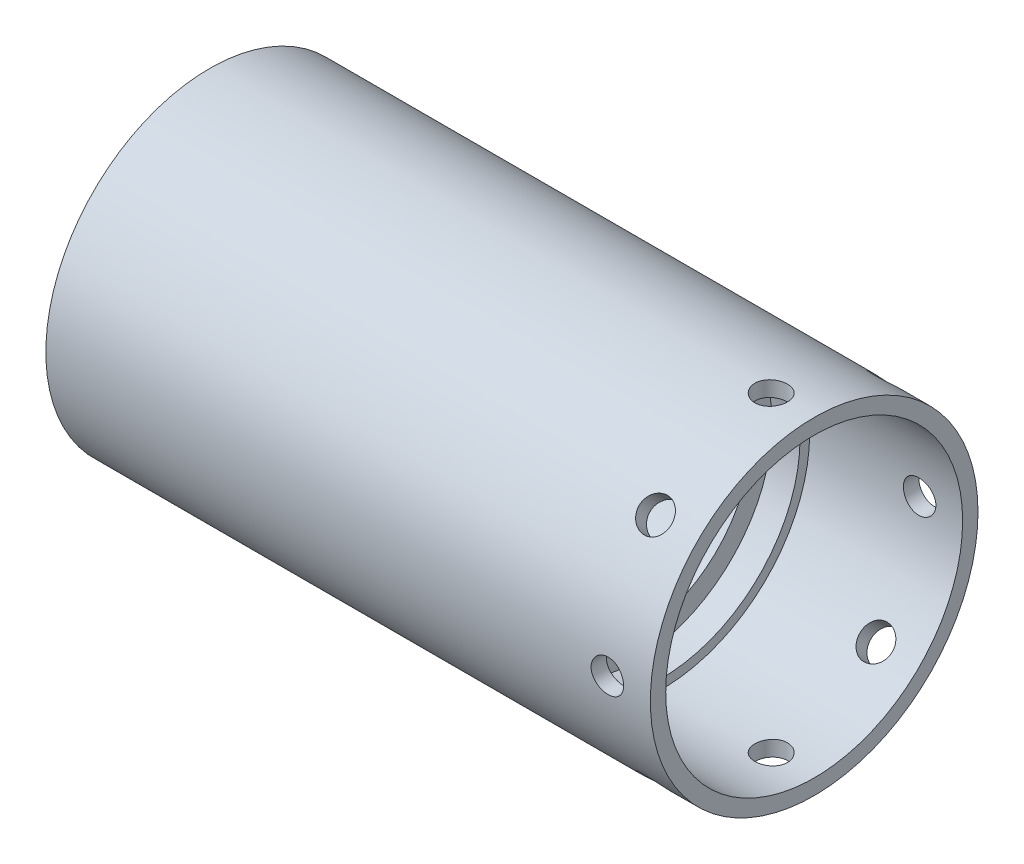
SolidWorks part; units mm, degrees
ref_plane "Front Plane" through (0, 0, 0) normal (0, 0, 1) x (1, 0, 0)
ref_plane "Top Plane" through (0, 0, 0) normal (0, 1, 0) x (1, 0, 0)
ref_plane "Right Plane" through (0, 0, 0) normal (1, 0, 0) x (0, 0, -1)
sketch "Sketch1" plane through (0, 0, 0) normal (1, 0, 0) x (0, 0, -1)
  circle A0 centre (0, 0) radius 50.8
  circle A1 centre (0, 0) radius 46.0375
  circle A2 centre (0, 0) radius 36.4109
  circle A4 centre (0, 0) radius 45.847
  circle A5 centre (0, 0) radius 42.8625
  dimension "D1" = 101.6
  dimension "D2" = 92.075
  dimension "D3" = 72.8218
  dimension "D4" = 91.694
  dimension "D5" = 85.725
extrude "Boss-Extrude1" add sketch "Sketch1" against normal blind 131.572 and the other way blind 55.88 contours A0 A1 region at (0, 0, 49.3632)
extrude "Boss-Extrude2" add sketch "Sketch1<3>" against normal blind 131.572 and the other way blind 8.636 separate body contours A4 A5 region at (0, 0, 44.5503)
sketch "Sketch1<3>" plane through (0, 0, 0) normal (1, 0, 0) x (0, 0, -1) same geometry as "Sketch1"
sketch "Sketch2" plane through (0, 0, 0) normal (0, 0, 1) x (1, 0, 0)
  line L0 (55.88, -50.8) -> (55.88, 50.8) construction
  point P0 (42.545, 0)
  dimension "D1" = 13.335
hole_wizard "Tap Drill for 3/8 Helicoil1" positions "Sketch2" profile "Sketch3" hole size "3/8-16" standard "ANSI Inch" end condition through all
sketch "Sketch3" plane through (42.545, 0, 0) normal (1, 0, 0) x (0, -1, 0)
  line L0 (0, 0) -> (0, 50.8)
  line L1 (0, 50.8) -> (5.0419, 50.8)
  line L2 (5.0419, 50.8) -> (5.0419, 0)
  line L5 (5.0419, 0) -> (0, 0)
  line L11 (0, -6.35) -> (0, 107.95) construction
  dimension "Thru Hole Dia." = 10.0838
  dimension "Thru Hole Depth" = 50.8
ref_axis "Axis1" through (74.6074, 0, 0) along (-1, 0, 0)
pattern_circular "CirPattern1" count 8 over 360 about axis through (74.6074, 0, 0) along (-1, 0, 0) of "Tap Drill for 3/8 Helicoil1"
extrude "Boss-Extrude4" add sketch "Sketch1<5>" against normal up to surface (131.572 mm away) separate body contours A5 A2 region at (0, 0, 41.6502) up to face at (-131.572, 0, -42.8625)
sketch "Sketch1<5>" plane through (0, 0, 0) normal (1, 0, 0) x (0, 0, -1) same geometry as "Sketch1"
